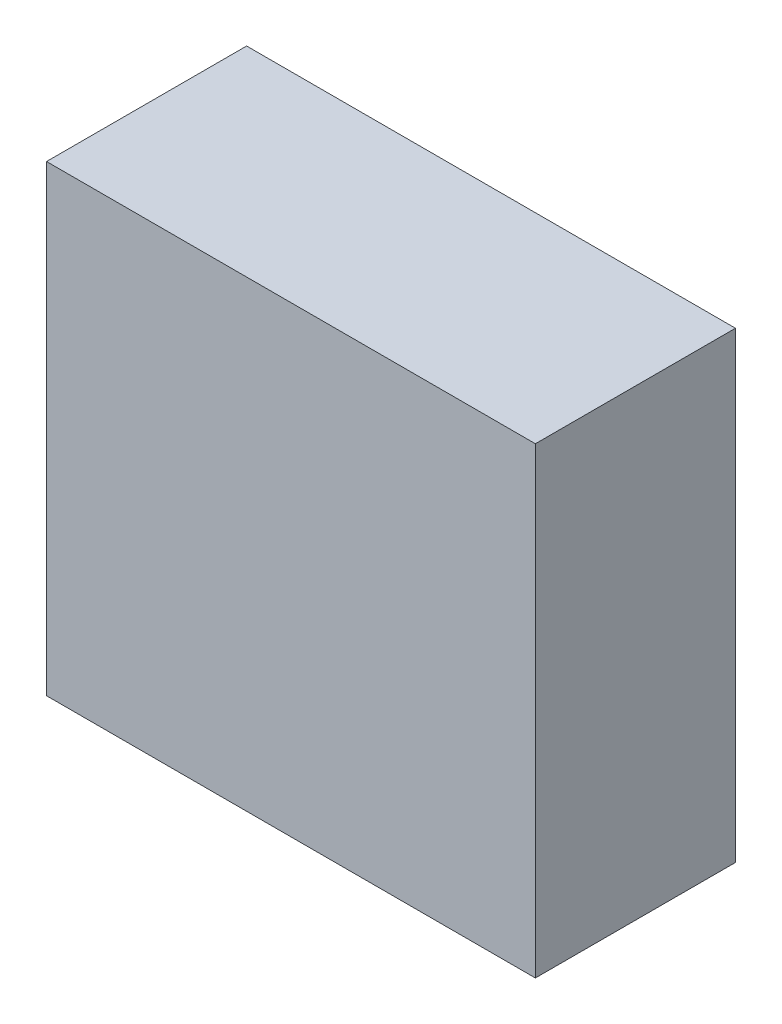
SolidWorks part; units mm, degrees
ref_plane "Front Plane" through (0, 0, 0) normal (0, 0, 1) x (1, 0, 0)
ref_plane "Top Plane" through (0, 0, 0) normal (0, 1, 0) x (1, 0, 0)
ref_plane "Right Plane" through (0, 0, 0) normal (1, 0, 0) x (0, 0, -1)
sketch "Sketch1" plane through (0, 0, 0) normal (0, 0, 1) x (1, 0, 0)
  line L1 (-21.5, -20.35) -> (21.5, -20.35)
  line L2 (-21.5, -20.35) -> (-21.5, 20.35)
  line L3 (-21.5, 20.35) -> (21.5, 20.35)
  line L4 (21.5, -20.35) -> (21.5, 20.35)
  line L5 (-21.5, -20.35) -> (21.5, 20.35) construction
  line L6 (-21.5, 20.35) -> (21.5, -20.35) construction
  point P0 (0, 0)
extrude "Envelope" add sketch "Sketch1" along normal blind 17.6
